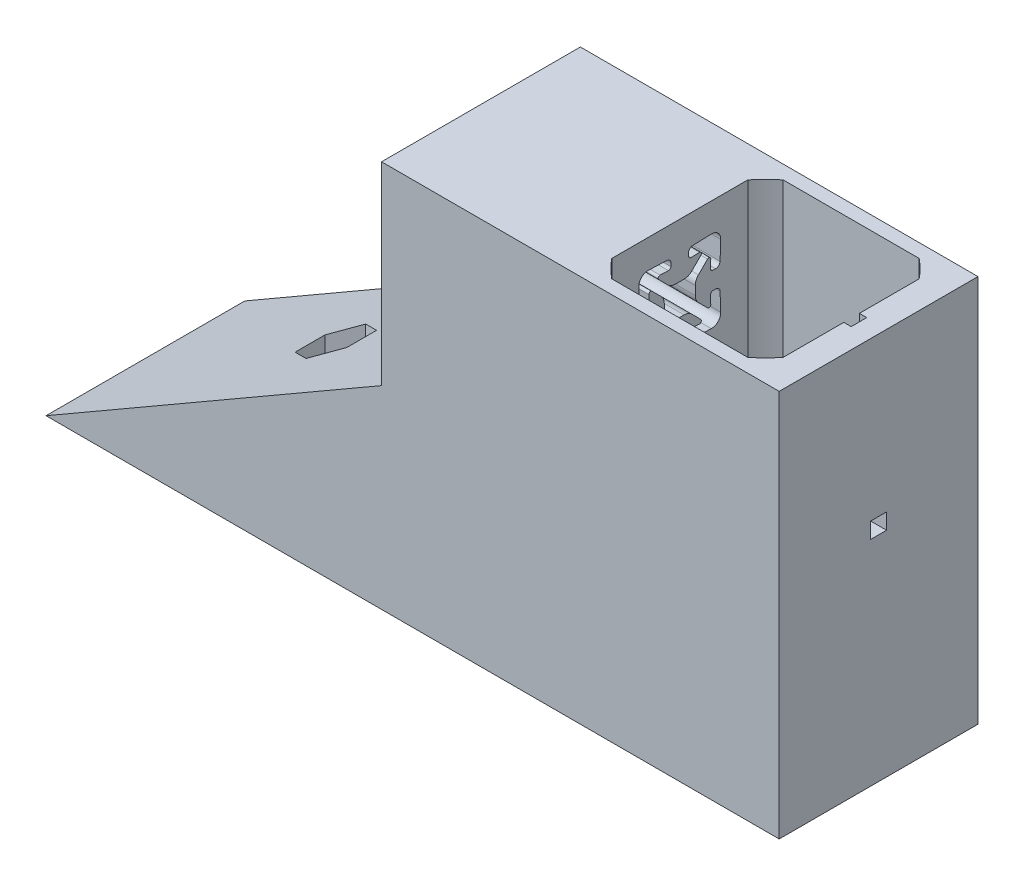
SolidWorks part; units mm, degrees
ref_plane "Front Plane" through (0, 0, 0) normal (1, 0, 0) x (0, 1, 0)
ref_plane "Top Plane" through (0, 0, 0) normal (0, 0, 1) x (0, 1, 0)
ref_plane "Right Plane" through (0, 0, 0) normal (0, 1, 0) x (-1, 0, 0)
sketch "Sketch1" plane through (0, 0, 0) normal (1, 0, 0) x (0, 1, 0)
  line L0 (76.1, 306.1022) -> (76.1, 303.8978)
  line L1 (75.3092, 301.9886) -> (73.0083, 299.6877)
  line L2 (72.2061, 300.0365) -> (72.2801, 302.1543)
  line L3 (71.7014, 302.7749) -> (71.0018, 302.7993)
  line L4 (69.8641, 301.7384) -> (69.7014, 297.0803)
  line L5 (72.0803, 294.7014) -> (76.7384, 294.8641)
  line L6 (77.7993, 296.0018) -> (77.7749, 296.7014)
  line L7 (77.1543, 297.2801) -> (75.0365, 297.2061)
  line L8 (74.6877, 298.0083) -> (76.9886, 300.3092)
  line L9 (78.8978, 301.1) -> (81.1022, 301.1)
  line L10 (83.0114, 300.3092) -> (85.3123, 298.0083)
  line L11 (84.9635, 297.2061) -> (82.8457, 297.2801)
  line L12 (82.2251, 296.7014) -> (82.2007, 296.0018)
  line L13 (83.2616, 294.8641) -> (87.9197, 294.7014)
  line L14 (90.2986, 297.0803) -> (90.1359, 301.7384)
  line L15 (88.9982, 302.7993) -> (88.2986, 302.7749)
  line L16 (87.7199, 302.1543) -> (87.7939, 300.0365)
  line L17 (86.9917, 299.6877) -> (84.6908, 301.9886)
  line L18 (83.9, 303.8978) -> (83.9, 306.1022)
  line L19 (84.6908, 308.0114) -> (86.9917, 310.3123)
  line L20 (87.7939, 309.9635) -> (87.7199, 307.8457)
  line L21 (88.2986, 307.2251) -> (88.9982, 307.2007)
  line L22 (90.1359, 308.2616) -> (90.2986, 312.9197)
  line L23 (87.9197, 315.2986) -> (83.2616, 315.1359)
  line L24 (82.2007, 313.9982) -> (82.2251, 313.2986)
  line L25 (82.8457, 312.7199) -> (84.9635, 312.7939)
  line L26 (85.3123, 311.9917) -> (83.0114, 309.6908)
  line L27 (81.1022, 308.9) -> (78.8978, 308.9)
  line L28 (76.9886, 309.6908) -> (74.6877, 311.9917)
  line L29 (75.0365, 312.7939) -> (77.1543, 312.7199)
  line L30 (77.7749, 313.2986) -> (77.7993, 313.9982)
  line L31 (76.7384, 315.1359) -> (72.0803, 315.2986)
  line L32 (69.7014, 312.9197) -> (69.8641, 308.2616)
  line L33 (71.0018, 307.2007) -> (71.7014, 307.2251)
  line L34 (72.2801, 307.8457) -> (72.2061, 309.9635)
  line L35 (73.0083, 310.3123) -> (75.3092, 308.0114)
  line L36 (76.4, 306.1022) -> (76.4, 303.8978)
  line L37 (75.5213, 301.7764) -> (73.2204, 299.4756)
  line L38 (71.9063, 300.047) -> (71.9802, 302.1648)
  line L39 (71.6909, 302.4751) -> (70.9913, 302.4995)
  line L40 (70.1639, 301.7279) -> (70.0012, 297.0698)
  line L41 (72.0698, 295.0012) -> (76.7279, 295.1639)
  line L42 (77.4995, 295.9913) -> (77.4751, 296.6909)
  line L43 (77.1648, 296.9802) -> (75.047, 296.9063)
  line L44 (74.4756, 298.2204) -> (76.7764, 300.5213)
  line L45 (78.8978, 301.4) -> (81.1022, 301.4)
  line L46 (83.2236, 300.5213) -> (85.5244, 298.2204)
  line L47 (84.953, 296.9063) -> (82.8352, 296.9802)
  line L48 (82.5249, 296.6909) -> (82.5005, 295.9913)
  line L49 (83.2721, 295.1639) -> (87.9302, 295.0012)
  line L50 (89.9988, 297.0698) -> (89.8361, 301.7279)
  line L51 (89.0087, 302.4995) -> (88.3091, 302.4751)
  line L52 (88.0198, 302.1648) -> (88.0937, 300.047)
  line L53 (86.7796, 299.4756) -> (84.4787, 301.7764)
  line L54 (83.6, 303.8978) -> (83.6, 306.1022)
  line L55 (84.4787, 308.2236) -> (86.7796, 310.5244)
  line L56 (88.0937, 309.953) -> (88.0198, 307.8352)
  line L57 (88.3091, 307.5249) -> (89.0087, 307.5005)
  line L58 (89.8361, 308.2721) -> (89.9988, 312.9302)
  line L59 (87.9302, 314.9988) -> (83.2721, 314.8361)
  line L60 (82.5005, 314.0087) -> (82.5249, 313.3091)
  line L61 (82.8352, 313.0198) -> (84.953, 313.0937)
  line L62 (85.5244, 311.7796) -> (83.2236, 309.4787)
  line L63 (81.1022, 308.6) -> (78.8978, 308.6)
  line L64 (76.7764, 309.4787) -> (74.4756, 311.7796)
  line L65 (75.047, 313.0937) -> (77.1648, 313.0198)
  line L66 (77.4751, 313.3091) -> (77.4995, 314.0087)
  line L67 (76.7279, 314.8361) -> (72.0698, 314.9988)
  line L68 (70.0012, 312.9302) -> (70.1639, 308.2721)
  line L69 (70.9913, 307.5005) -> (71.6909, 307.5249)
  line L70 (71.9802, 307.8352) -> (71.9063, 309.953)
  line L71 (73.2204, 310.5244) -> (75.5213, 308.2236)
  line L72 (76.4, 306.1022) -> (76.4, 303.8978)
  line L73 (75.5213, 301.7764) -> (73.2204, 299.4756)
  line L74 (71.9063, 300.047) -> (71.9802, 302.1648)
  line L75 (71.6909, 302.4751) -> (70.9913, 302.4995)
  line L76 (70.1639, 301.7279) -> (70.0012, 297.0698)
  line L77 (72.0698, 295.0012) -> (76.7279, 295.1639)
  line L78 (77.4995, 295.9913) -> (77.4751, 296.6909)
  line L79 (77.1648, 296.9802) -> (75.047, 296.9063)
  line L80 (74.4756, 298.2204) -> (76.7764, 300.5213)
  line L81 (78.8978, 301.4) -> (81.1022, 301.4)
  line L82 (83.2236, 300.5213) -> (85.5244, 298.2204)
  line L83 (84.953, 296.9063) -> (82.8352, 296.9802)
  line L84 (82.5249, 296.6909) -> (82.5005, 295.9913)
  line L85 (83.2721, 295.1639) -> (87.9302, 295.0012)
  line L86 (89.9988, 297.0698) -> (89.8361, 301.7279)
  line L87 (89.0087, 302.4995) -> (88.3091, 302.4751)
  line L88 (88.0198, 302.1648) -> (88.0937, 300.047)
  line L89 (86.7796, 299.4756) -> (84.4787, 301.7764)
  line L90 (83.6, 303.8978) -> (83.6, 306.1022)
  line L91 (84.4787, 308.2236) -> (86.7796, 310.5244)
  line L92 (88.0937, 309.953) -> (88.0198, 307.8352)
  line L93 (88.3091, 307.5249) -> (89.0087, 307.5005)
  line L94 (89.8361, 308.2721) -> (89.9988, 312.9302)
  line L95 (87.9302, 314.9988) -> (83.2721, 314.8361)
  line L96 (82.5005, 314.0087) -> (82.5249, 313.3091)
  line L97 (82.8352, 313.0198) -> (84.953, 313.0937)
  line L98 (85.5244, 311.7796) -> (83.2236, 309.4787)
  line L99 (81.1022, 308.6) -> (78.8978, 308.6)
  line L100 (76.7764, 309.4787) -> (74.4756, 311.7796)
  line L101 (75.047, 313.0937) -> (77.1648, 313.0198)
  line L102 (77.4751, 313.3091) -> (77.4995, 314.0087)
  line L103 (76.7279, 314.8361) -> (72.0698, 314.9988)
  line L104 (70.0012, 312.9302) -> (70.1639, 308.2721)
  line L105 (70.9913, 307.5005) -> (71.6909, 307.5249)
  line L106 (71.9802, 307.8352) -> (71.9063, 309.953)
  line L107 (73.2204, 310.5244) -> (75.5213, 308.2236)
  line L108 (0, -325) -> (0, 325) construction
  line L113 (97.5, 280) -> (62.5, 280)
  line L114 (97.5, 280) -> (97.5, 330)
  line L115 (97.5, 330) -> (62.5, 330)
  line L116 (62.5, 280) -> (62.5, 330)
  line L117 (97.5, 280) -> (62.5, 330) construction
  line L118 (97.5, 330) -> (62.5, 280) construction
  line L119 (62.5, 330) -> (0, 330)
  line L120 (62.5, 330) -> (62.5, 280)
  line L121 (62.5, 280) -> (0, 280)
  line L122 (0, 330) -> (0, 280)
  arc A0 (75.3092, 301.9886) -> (76.1, 303.8978) centre (73.4, 303.8978) ccw
  arc A1 (72.2061, 300.0365) -> (73.0083, 299.6877) centre (72.6759, 300.0201) ccw
  arc A2 (72.2801, 302.1543) -> (71.7014, 302.7749) centre (71.6804, 302.1753) ccw
  arc A3 (71.0018, 302.7993) -> (69.8641, 301.7384) centre (70.9634, 301.7) ccw
  arc A4 (69.7014, 297.0803) -> (72.0803, 294.7014) centre (72, 297) ccw
  arc A5 (76.7384, 294.8641) -> (77.7993, 296.0018) centre (76.7, 295.9634) ccw
  arc A6 (77.7749, 296.7014) -> (77.1543, 297.2801) centre (77.1753, 296.6804) ccw
  arc A7 (74.6877, 298.0083) -> (75.0365, 297.2061) centre (75.0201, 297.6759) ccw
  arc A8 (78.8978, 301.1) -> (76.9886, 300.3092) centre (78.8978, 298.4) ccw
  arc A9 (83.0114, 300.3092) -> (81.1022, 301.1) centre (81.1022, 298.4) ccw
  arc A10 (84.9635, 297.2061) -> (85.3123, 298.0083) centre (84.9799, 297.6759) ccw
  arc A11 (82.8457, 297.2801) -> (82.2251, 296.7014) centre (82.8247, 296.6804) ccw
  arc A12 (82.2007, 296.0018) -> (83.2616, 294.8641) centre (83.3, 295.9634) ccw
  arc A13 (87.9197, 294.7014) -> (90.2986, 297.0803) centre (88, 297) ccw
  arc A14 (90.1359, 301.7384) -> (88.9982, 302.7993) centre (89.0366, 301.7) ccw
  arc A15 (88.2986, 302.7749) -> (87.7199, 302.1543) centre (88.3196, 302.1753) ccw
  arc A16 (86.9917, 299.6877) -> (87.7939, 300.0365) centre (87.3241, 300.0201) ccw
  arc A17 (83.9, 303.8978) -> (84.6908, 301.9886) centre (86.6, 303.8978) ccw
  arc A18 (84.6908, 308.0114) -> (83.9, 306.1022) centre (86.6, 306.1022) ccw
  arc A19 (87.7939, 309.9635) -> (86.9917, 310.3123) centre (87.3241, 309.9799) ccw
  arc A20 (87.7199, 307.8457) -> (88.2986, 307.2251) centre (88.3196, 307.8247) ccw
  arc A21 (88.9982, 307.2007) -> (90.1359, 308.2616) centre (89.0366, 308.3) ccw
  arc A22 (90.2986, 312.9197) -> (87.9197, 315.2986) centre (88, 313) ccw
  arc A23 (83.2616, 315.1359) -> (82.2007, 313.9982) centre (83.3, 314.0366) ccw
  arc A24 (82.2251, 313.2986) -> (82.8457, 312.7199) centre (82.8247, 313.3196) ccw
  arc A25 (85.3123, 311.9917) -> (84.9635, 312.7939) centre (84.9799, 312.3241) ccw
  arc A26 (81.1022, 308.9) -> (83.0114, 309.6908) centre (81.1022, 311.6) ccw
  arc A27 (76.9886, 309.6908) -> (78.8978, 308.9) centre (78.8978, 311.6) ccw
  arc A28 (75.0365, 312.7939) -> (74.6877, 311.9917) centre (75.0201, 312.3241) ccw
  arc A29 (77.1543, 312.7199) -> (77.7749, 313.2986) centre (77.1753, 313.3196) ccw
  arc A30 (77.7993, 313.9982) -> (76.7384, 315.1359) centre (76.7, 314.0366) ccw
  arc A31 (72.0803, 315.2986) -> (69.7014, 312.9197) centre (72, 313) ccw
  arc A32 (69.8641, 308.2616) -> (71.0018, 307.2007) centre (70.9634, 308.3) ccw
  arc A33 (71.7014, 307.2251) -> (72.2801, 307.8457) centre (71.6804, 307.8247) ccw
  arc A34 (73.0083, 310.3123) -> (72.2061, 309.9635) centre (72.6759, 309.9799) ccw
  arc A35 (76.1, 306.1022) -> (75.3092, 308.0114) centre (73.4, 306.1022) ccw
  arc A36 (75.5213, 301.7764) -> (76.4, 303.8978) centre (73.4, 303.8978) ccw
  arc A37 (71.9063, 300.047) -> (73.2204, 299.4756) centre (72.6759, 300.0201) ccw
  arc A38 (71.9802, 302.1648) -> (71.6909, 302.4751) centre (71.6804, 302.1753) ccw
  arc A39 (70.9913, 302.4995) -> (70.1639, 301.7279) centre (70.9634, 301.7) ccw
  arc A40 (70.0012, 297.0698) -> (72.0698, 295.0012) centre (72, 297) ccw
  arc A41 (76.7279, 295.1639) -> (77.4995, 295.9913) centre (76.7, 295.9634) ccw
  arc A42 (77.4751, 296.6909) -> (77.1648, 296.9802) centre (77.1753, 296.6804) ccw
  arc A43 (74.4756, 298.2204) -> (75.047, 296.9063) centre (75.0201, 297.6759) ccw
  arc A44 (78.8978, 301.4) -> (76.7764, 300.5213) centre (78.8978, 298.4) ccw
  arc A45 (83.2236, 300.5213) -> (81.1022, 301.4) centre (81.1022, 298.4) ccw
  arc A46 (84.953, 296.9063) -> (85.5244, 298.2204) centre (84.9799, 297.6759) ccw
  arc A47 (82.8352, 296.9802) -> (82.5249, 296.6909) centre (82.8247, 296.6804) ccw
  arc A48 (82.5005, 295.9913) -> (83.2721, 295.1639) centre (83.3, 295.9634) ccw
  arc A49 (87.9302, 295.0012) -> (89.9988, 297.0698) centre (88, 297) ccw
  arc A50 (89.8361, 301.7279) -> (89.0087, 302.4995) centre (89.0366, 301.7) ccw
  arc A51 (88.3091, 302.4751) -> (88.0198, 302.1648) centre (88.3196, 302.1753) ccw
  arc A52 (86.7796, 299.4756) -> (88.0937, 300.047) centre (87.3241, 300.0201) ccw
  arc A53 (83.6, 303.8978) -> (84.4787, 301.7764) centre (86.6, 303.8978) ccw
  arc A54 (84.4787, 308.2236) -> (83.6, 306.1022) centre (86.6, 306.1022) ccw
  arc A55 (88.0937, 309.953) -> (86.7796, 310.5244) centre (87.3241, 309.9799) ccw
  arc A56 (88.0198, 307.8352) -> (88.3091, 307.5249) centre (88.3196, 307.8247) ccw
  arc A57 (89.0087, 307.5005) -> (89.8361, 308.2721) centre (89.0366, 308.3) ccw
  arc A58 (89.9988, 312.9302) -> (87.9302, 314.9988) centre (88, 313) ccw
  arc A59 (83.2721, 314.8361) -> (82.5005, 314.0087) centre (83.3, 314.0366) ccw
  arc A60 (82.5249, 313.3091) -> (82.8352, 313.0198) centre (82.8247, 313.3196) ccw
  arc A61 (85.5244, 311.7796) -> (84.953, 313.0937) centre (84.9799, 312.3241) ccw
  arc A62 (81.1022, 308.6) -> (83.2236, 309.4787) centre (81.1022, 311.6) ccw
  arc A63 (76.7764, 309.4787) -> (78.8978, 308.6) centre (78.8978, 311.6) ccw
  arc A64 (75.047, 313.0937) -> (74.4756, 311.7796) centre (75.0201, 312.3241) ccw
  arc A65 (77.1648, 313.0198) -> (77.4751, 313.3091) centre (77.1753, 313.3196) ccw
  arc A66 (77.4995, 314.0087) -> (76.7279, 314.8361) centre (76.7, 314.0366) ccw
  arc A67 (72.0698, 314.9988) -> (70.0012, 312.9302) centre (72, 313) ccw
  arc A68 (70.1639, 308.2721) -> (70.9913, 307.5005) centre (70.9634, 308.3) ccw
  arc A69 (71.6909, 307.5249) -> (71.9802, 307.8352) centre (71.6804, 307.8247) ccw
  arc A70 (73.2204, 310.5244) -> (71.9063, 309.953) centre (72.6759, 309.9799) ccw
  arc A71 (76.4, 306.1022) -> (75.5213, 308.2236) centre (73.4, 306.1022) ccw
  arc A72 (75.5213, 301.7764) -> (76.4, 303.8978) centre (73.4, 303.8978) ccw
  arc A73 (71.9063, 300.047) -> (73.2204, 299.4756) centre (72.6759, 300.0201) ccw
  arc A74 (71.9802, 302.1648) -> (71.6909, 302.4751) centre (71.6804, 302.1753) ccw
  arc A75 (70.9913, 302.4995) -> (70.1639, 301.7279) centre (70.9634, 301.7) ccw
  arc A76 (70.0012, 297.0698) -> (72.0698, 295.0012) centre (72, 297) ccw
  arc A77 (76.7279, 295.1639) -> (77.4995, 295.9913) centre (76.7, 295.9634) ccw
  arc A78 (77.4751, 296.6909) -> (77.1648, 296.9802) centre (77.1753, 296.6804) ccw
  arc A79 (74.4756, 298.2204) -> (75.047, 296.9063) centre (75.0201, 297.6759) ccw
  arc A80 (78.8978, 301.4) -> (76.7764, 300.5213) centre (78.8978, 298.4) ccw
  arc A81 (83.2236, 300.5213) -> (81.1022, 301.4) centre (81.1022, 298.4) ccw
  arc A82 (84.953, 296.9063) -> (85.5244, 298.2204) centre (84.9799, 297.6759) ccw
  arc A83 (82.8352, 296.9802) -> (82.5249, 296.6909) centre (82.8247, 296.6804) ccw
  arc A84 (82.5005, 295.9913) -> (83.2721, 295.1639) centre (83.3, 295.9634) ccw
  arc A85 (87.9302, 295.0012) -> (89.9988, 297.0698) centre (88, 297) ccw
  arc A86 (89.8361, 301.7279) -> (89.0087, 302.4995) centre (89.0366, 301.7) ccw
  arc A87 (88.3091, 302.4751) -> (88.0198, 302.1648) centre (88.3196, 302.1753) ccw
  arc A88 (86.7796, 299.4756) -> (88.0937, 300.047) centre (87.3241, 300.0201) ccw
  arc A89 (83.6, 303.8978) -> (84.4787, 301.7764) centre (86.6, 303.8978) ccw
  arc A90 (84.4787, 308.2236) -> (83.6, 306.1022) centre (86.6, 306.1022) ccw
  arc A91 (88.0937, 309.953) -> (86.7796, 310.5244) centre (87.3241, 309.9799) ccw
  arc A92 (88.0198, 307.8352) -> (88.3091, 307.5249) centre (88.3196, 307.8247) ccw
  arc A93 (89.0087, 307.5005) -> (89.8361, 308.2721) centre (89.0366, 308.3) ccw
  arc A94 (89.9988, 312.9302) -> (87.9302, 314.9988) centre (88, 313) ccw
  arc A95 (83.2721, 314.8361) -> (82.5005, 314.0087) centre (83.3, 314.0366) ccw
  arc A96 (82.5249, 313.3091) -> (82.8352, 313.0198) centre (82.8247, 313.3196) ccw
  arc A97 (85.5244, 311.7796) -> (84.953, 313.0937) centre (84.9799, 312.3241) ccw
  arc A98 (81.1022, 308.6) -> (83.2236, 309.4787) centre (81.1022, 311.6) ccw
  arc A99 (76.7764, 309.4787) -> (78.8978, 308.6) centre (78.8978, 311.6) ccw
  arc A100 (75.047, 313.0937) -> (74.4756, 311.7796) centre (75.0201, 312.3241) ccw
  arc A101 (77.1648, 313.0198) -> (77.4751, 313.3091) centre (77.1753, 313.3196) ccw
  arc A102 (77.4995, 314.0087) -> (76.7279, 314.8361) centre (76.7, 314.0366) ccw
  arc A103 (72.0698, 314.9988) -> (70.0012, 312.9302) centre (72, 313) ccw
  arc A104 (70.1639, 308.2721) -> (70.9913, 307.5005) centre (70.9634, 308.3) ccw
  arc A105 (71.6909, 307.5249) -> (71.9802, 307.8352) centre (71.6804, 307.8247) ccw
  arc A106 (73.2204, 310.5244) -> (71.9063, 309.953) centre (72.6759, 309.9799) ccw
  arc A107 (76.4, 306.1022) -> (75.5213, 308.2236) centre (73.4, 306.1022) ccw
  point P216 (80, 305)
  point P217 (80, 305)
  dimension "D3" = 50
  dimension "D4" = 35
  dimension "D1" = 0
  dimension "D2" = 0.3
extrude "Boss-Extrude1" add sketch "Sketch1" against normal blind 50 contours L116 L113 L114 L115 L0 A35 L35 A34 L34 A33 L33 A32 L32 A31 L31 A30 L30 A29 L29 A28 L28 A27 L27 A26 L26 A25 L25 A24 L24 A23 L23 A22 L22 A21 L21 A20 L20 A19 L19 A18 L18 A17 L17 A16 L16 A15 L15 A14 L14 A13 | L119 L122 L121 L116 region at (0, 80, 280.6103) region at (0, 31.25, 305)
sketch "Sketch2" plane through (0, 0, 280) normal (0, 0, -1) x (1, 0, 0)
  line L0 (-50, -48.75) -> (-134.386, 0)
  line L1 (-50, -97.5) -> (-50, 0) construction
  line L3 (-50, -48.75) -> (-50, 0)
  line L4 (-50, 0) -> (-134.386, 0)
extrude "Boss-Extrude2" add sketch "Sketch2" against normal up to surface (50 mm away) up to face at (-25, 48.75, 330)
sketch "Sketch3" plane through (0, 97.5, 0) normal (0, 1, 0) x (-1, 0, 0)
  line L0 (0, 305) -> (134.386, 305) construction
  line L1 (0, 280) -> (0, 330) construction
  line L2 (134.386, 330) -> (134.386, 280) construction
  line L5 (67.9904, 308.75) -> (61.4952, 312.5)
  line L6 (92.9904, 308.75) -> (86.4952, 312.5)
  line L7 (86.4952, 312.5) -> (80, 308.75)
  line L8 (80, 308.75) -> (80, 301.25)
  line L9 (80, 301.25) -> (86.4952, 297.5)
  line L10 (86.4952, 297.5) -> (92.9904, 301.25)
  line L11 (92.9904, 301.25) -> (92.9904, 308.75)
  line L12 (61.4952, 312.5) -> (55, 308.75)
  line L13 (55, 308.75) -> (55, 301.25)
  line L14 (55, 301.25) -> (61.4952, 297.5)
  line L15 (61.4952, 297.5) -> (67.9904, 301.25)
  line L16 (67.9904, 301.25) -> (67.9904, 308.75)
  line L17 (92.9904, 308.75) -> (67.9904, 308.75) construction
  circle A0 centre (86.4952, 305) radius 6.4952 construction
  dimension "D1" = 15
  dimension "D3" = 25
  dimension "D4" = 30
  dimension "D2" = 2
extrude "Cut-Extrude1" cut sketch "Sketch3" against normal blind 81
sketch "Sketch4" plane through (0, 47.494, 0) normal (0, -1, 0) x (1, 0, 0)
  line L1 (4.55, 326.25) -> (38.55, 326.25) construction
  line L2 (38.55, 283.75) -> (4.55, 283.75) construction
  line L3 (42.8, 322) -> (42.8, 288) construction
  line L4 (0.3, 288) -> (0.3, 322) construction
  line L5 (4.55, 326.25) -> (38.55, 326.25)
  line L6 (38.55, 283.75) -> (4.55, 283.75)
  line L7 (42.8, 322) -> (42.8, 288)
  line L8 (0.3, 288) -> (0.3, 322)
  line L9 (4.4452, 326.55) -> (38.6548, 326.55)
  line L10 (43.1, 322.1048) -> (43.1, 287.8952)
  line L11 (38.6548, 283.45) -> (4.4452, 283.45)
  line L12 (0, 287.8952) -> (0, 322.1048)
  line L13 (50, -325) -> (50, 325) construction
  line L14 (0, 330) -> (50, 330)
  line L15 (0, 330) -> (0, 280)
  line L16 (0, 280) -> (50, 280)
  line L17 (50, 330) -> (50, 280)
  line L18 (-134.386, 280) -> (0, 280) construction
  line L20 (42.8, 306.8555) -> (44.9533, 306.8555)
  line L21 (42.8, 306.8555) -> (42.8, 302.9224)
  line L22 (42.8, 302.9224) -> (44.9533, 302.9224)
  line L23 (44.9533, 306.8555) -> (44.9533, 302.9224)
  arc A0 (0.3, 288) -> (4.55, 283.75) centre (21.3983, 304.8483) ccw construction
  arc A1 (4.55, 326.25) -> (0.3, 322) centre (21.3983, 305.1517) ccw construction
  arc A2 (38.55, 283.75) -> (42.8, 288) centre (21.7017, 304.8483) ccw construction
  arc A3 (42.8, 322) -> (38.55, 326.25) centre (21.7017, 305.1517) ccw construction
  arc A4 (0.3, 288) -> (4.55, 283.75) centre (21.3983, 304.8483) ccw
  arc A5 (4.55, 326.25) -> (0.3, 322) centre (21.3983, 305.1517) ccw
  arc A6 (38.55, 283.75) -> (42.8, 288) centre (21.7017, 304.8483) ccw
  arc A7 (42.8, 322) -> (38.55, 326.25) centre (21.7017, 305.1517) ccw
  arc A8 (43.1, 322.1048) -> (38.6548, 326.55) centre (21.7017, 305.1517) ccw
  arc A9 (38.6548, 283.45) -> (43.1, 287.8952) centre (21.7017, 304.8483) ccw
  arc A10 (0, 287.8952) -> (4.4452, 283.45) centre (21.3983, 304.8483) ccw
  arc A11 (4.4452, 326.55) -> (0, 322.1048) centre (21.3983, 305.1517) ccw
  dimension "D1" = 0.3
extrude "Boss-Extrude3" add sketch "Sketch4" against normal up to surface (50.006 mm away) contours A11 L9 A8 L10 A9 L11 A10 L15 L16 L17 L14 region at (43.8071, 47.494, 314.4801) up to face at (-25, 97.5, 305)
sketch "Sketch5" plane through (44.9533, 0, 0) normal (-1, 0, 0) x (0, -1, 0)
  line L0 (0, 330) -> (-97.5, 280) construction
  line L1 (-97.5, 280) -> (-47.494, 280) construction
  line L2 (-97.5, 280) -> (-97.5, 330) construction
  line L3 (-97.5, 330) -> (0, 280) construction
  line L4 (0, 280) -> (-48.75, 305) construction
  line L5 (-48.75, 305) -> (-47.494, 305) construction
  line L6 (-47.494, 330) -> (-47.494, 280) construction
  line L7 (-55.75, 305) -> (-48.75, 305) construction
  line L8 (-57.75, 303) -> (-53.75, 303)
  line L9 (-57.75, 303) -> (-57.75, 307)
  line L10 (-57.75, 307) -> (-53.75, 307)
  line L11 (-53.75, 303) -> (-53.75, 307)
  line L12 (-57.75, 303) -> (-53.75, 307) construction
  line L13 (-57.75, 307) -> (-53.75, 303) construction
  line L14 (-97.5, 280) -> (-48.75, 280) construction
  line L15 (-97.5, 280) -> (-97.5, 330) construction
  line L16 (-97.5, 330) -> (-48.75, 330) construction
  point P5 (-55.75, 305)
  point P18 (0, 0)
  point P21 (0, 0)
  point P24 (0, 0)
  point P25 (-95.8854, 280)
  point P26 (0, 0)
  point P29 (0, 0)
  dimension "D1" = 4
  dimension "D2" = 4
  dimension "D3" = 7
extrude "Cut-Extrude2" cut sketch "Sketch5" against normal blind 30
sketch "Sketch6" plane through (0, 0, 0) normal (1, 0, 0) x (0, 1, 0)
  line L0 (47.494, 322.1048) -> (47.494, 287.8952)
  line L8 (47.494, 287.8952) -> (97.5, 287.8952)
  line L9 (97.5, 287.8952) -> (97.5, 322.1048)
  line L10 (97.5, 322.1048) -> (47.494, 322.1048)
  line L11 (47.494, 322.1048) -> (47.494, 330)
  line L12 (47.494, 330) -> (0, 330)
  line L13 (0, 330) -> (0, 280)
  line L14 (0, 280) -> (47.494, 280)
  line L15 (47.494, 280) -> (47.494, 287.8952)
  line L16 (47.494, 287.8952) -> (97.5, 287.8952)
  line L17 (97.5, 287.8952) -> (97.5, 322.1048)
  line L18 (97.5, 322.1048) -> (47.494, 322.1048)
  line L19 (47.494, 322.1048) -> (47.494, 330)
  line L20 (47.494, 330) -> (0, 330)
  line L21 (0, 330) -> (0, 280)
  line L22 (0, 280) -> (47.494, 280)
  line L23 (47.494, 280) -> (47.494, 287.8952)
  dimension "D1" = 0
extrude "Boss-Extrude4" add sketch "Sketch6" along normal up to surface (50 mm away) contours L22 L23 L0 L19 L20 L21 region at (0, 23.747, 305) up to face at (50, 55.75, 305)
